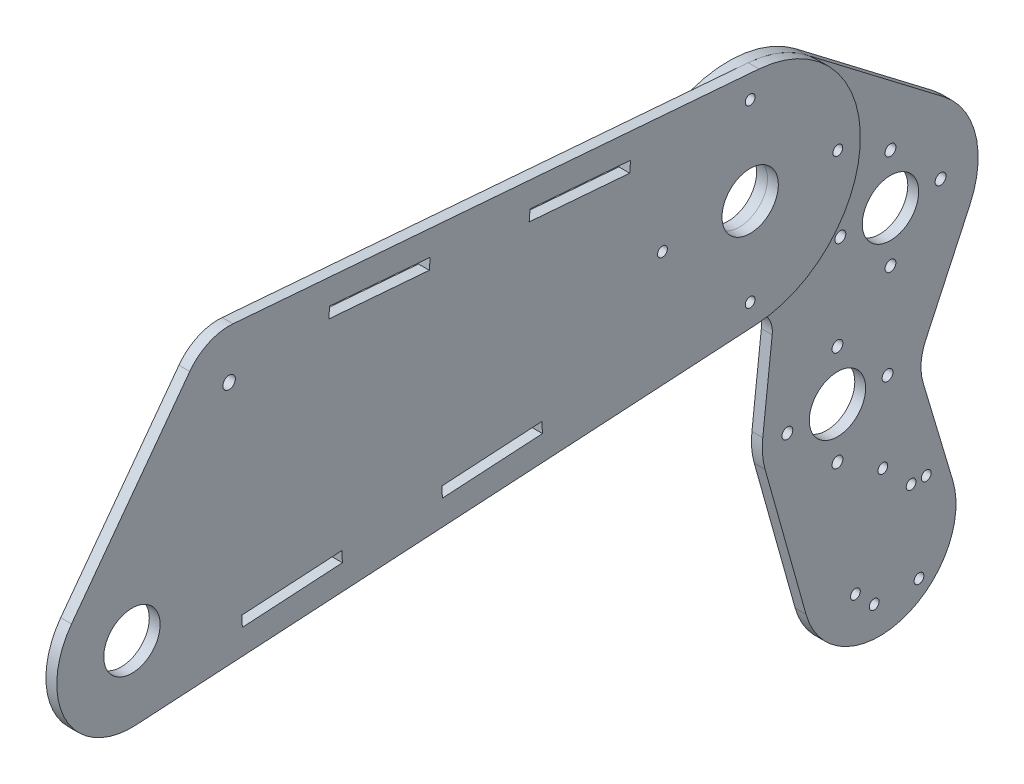
SolidWorks part; units mm, degrees
ref_plane "Alzado" through (0, 0, 0) normal (0, 0, 1) x (1, 0, 0)
ref_plane "Planta" through (0, 0, 0) normal (0, 1, 0) x (1, 0, 0)
ref_plane "Vista lateral" through (0, 0, 0) normal (1, 0, 0) x (0, 0, -1)
sketch "Llantas" plane through (0, 0, 0) normal (1, 0, 0) x (0, 0, -1)
  line L0 (-207.2231, -76.2) -> (-590.1805, -76.2) construction
  line L1 (-359.537, 40.64) -> (359.537, 40.64)
  line L2 (-359.537, 40.64) -> (-359.537, -40.64)
  line L3 (-359.537, -40.64) -> (359.537, -40.64)
  line L4 (359.537, 40.64) -> (359.537, -40.64)
  line L5 (-359.537, 40.64) -> (359.537, -40.64) construction
  line L6 (-359.537, -40.64) -> (359.537, 40.64) construction
  line L7 (-359.537, 101.6) -> (-416.687, 101.6)
  line L8 (-448.437, 69.85) -> (-448.437, 6.35)
  line L9 (-416.687, -25.4) -> (-359.537, -25.4)
  line L10 (-359.537, 101.6) -> (-359.537, -25.4)
  circle A0 centre (-677.037, 152.4) radius 50.8
  circle A2 centre (-207.2231, 0) radius 76.2
  arc A3 (-416.687, 101.6) -> (-448.437, 69.85) centre (-416.687, 69.85) ccw
  arc A4 (-448.437, 6.35) -> (-416.687, -25.4) centre (-416.687, 6.35) ccw
  point P3 (0, 0)
  dimension "D1" = 101.6
  dimension "D5" = 152.4
  dimension "D6" = 177.8
  dimension "D4" = 31.75
  dimension "D11" = 177.8
  dimension "D2" = 81.28
  dimension "D3" = 719.074
  dimension "D7" = 35.56
  dimension "D8" = 88.9
  dimension "D9" = 127
  dimension "D10" = 50.8
sketch "TP" plane through (0, 0, 0) normal (1, 0, 0) x (0, 0, -1)
  line L0 (-365.8418, 207.7402) -> (-679.2386, 171.3713) construction
  line L1 (-361.4386, 169.7977) -> (-674.8354, 133.4287) construction
  line L2 (-289.879, 135.5242) -> (-372.2396, 161.4422) construction
  line L3 (-307.9621, 190.476) -> (-304.3358, 72.1959) construction
  line L4 (-344.3178, 209.9195) -> (-280.5717, 151.6834) construction
  line L5 (-403.4591, 149.8149) -> (-320.7067, 65.2254) construction
  arc A0 (-679.2386, 171.3713) -> (-674.8354, 133.4287) centre (-677.037, 152.4) ccw construction
  arc A2 (-344.3178, 209.9195) -> (-372.2396, 161.4422) centre (-363.6402, 188.7689) ccw construction
  circle A4 centre (-287.0125, 144.6332) radius 30
  arc A5 (-289.879, 135.5242) -> (-280.5717, 151.6834) centre (-287.0125, 144.6332) ccw construction
  arc A7 (-361.4386, 169.7977) -> (-365.8418, 207.7402) centre (-363.6402, 188.7689) ccw construction
  arc A8 (-307.9621, 190.476) -> (-403.4591, 149.8149) centre (-363.6402, 188.7689) ccw construction
  circle A9 centre (-313.8806, 71.9033) radius 30
  arc A10 (-320.7067, 65.2254) -> (-304.3358, 72.1959) centre (-313.8806, 71.9033) ccw construction
  dimension "D1" = 38.1972
  dimension "D2" = 57.2958
  dimension "D3" = 19.0986
  dimension "D4" = 60
  dimension "D5" = 38.1972
  dimension "D8" = 111.4085
  dimension "D9" = 60
  dimension "D10" = 19.0986
sketch "Placa" plane through (0, 0, 0) normal (1, 0, 0) x (0, 0, -1)
  line L0 (-621.0491, 130.2708) -> (-417.8491, 142.3033)
  line L1 (-674.7849, 114.3666) -> (-360.3371, 132.9867)
  line L2 (-329.7252, 233.1801) -> (-260.0347, 179.9602)
  line L3 (-346.965, 118.8981) -> (-351.7448, 76.1356)
  line L4 (-350.566, 61.6178) -> (-329.8243, -12.3619)
  line L5 (-246.7183, 125.8667) -> (-279.3428, 55.8177)
  line L6 (-277.3702, 82.7937) -> (-255.4086, 9.167)
  line L7 (-359.537, 40.64) -> (-359.537, -40.64) construction
  line L8 (-359.537, 40.64) -> (359.537, 40.64) construction
  line L9 (-359.537, -40.64) -> (359.537, -40.64) construction
  line L10 (-647.7191, 255.9522) -> (-707.6477, 175.0847)
  line L11 (-625.7904, 265.9135) -> (-359.1604, 244.4691)
  line L12 (-418.1742, 147.7937) -> (-621.3742, 135.7612)
  line L13 (-621.3742, 135.7612) -> (-621.0491, 130.2708)
  line L14 (-418.1742, 147.7937) -> (-417.8491, 142.3033)
  line L15 (-627.4528, 253.3062) -> (-424.2528, 236.9633)
  line L16 (-424.2528, 236.9633) -> (-424.6937, 231.481)
  line L17 (-424.6937, 231.481) -> (-627.8937, 247.8239)
  line L18 (-627.8937, 247.8239) -> (-627.4528, 253.3062)
  line L19 (-570.663, 138.7641) -> (-570.3379, 133.2737)
  line L20 (-519.9519, 141.7669) -> (-519.6267, 136.2766)
  line L22 (-469.2407, 144.7698) -> (-468.9156, 139.2794)
  line L23 (-576.8163, 249.2336) -> (-577.2572, 243.7513)
  line L24 (-525.8528, 245.1347) -> (-526.2937, 239.6524)
  line L25 (-475.6572, 235.5799) -> (-475.2163, 241.0622)
  circle A0 centre (-677.037, 152.4) radius 14.2875
  circle A1 centre (-363.6402, 188.7689) radius 14.2875
  circle A3 centre (-287.0125, 144.6332) radius 14.2875
  circle A4 centre (-313.8806, 71.9033) radius 14.2875
  circle A5 centre (-677.037, 152.4) radius 38.1
  circle A6 centre (-313.8806, 71.9033) radius 38.1
  circle A7 centre (-287.0125, 144.6332) radius 44.45
  circle A8 centre (-363.6402, 188.7689) radius 55.88
  arc A9 (-346.965, 118.8981) -> (-360.3371, 132.9867) centre (-359.5863, 120.3089) ccw
  circle A15 centre (-313.8806, 71.9033) radius 25.4 construction
  circle A16 centre (-313.8806, 97.3033) radius 2.75
  circle A17 centre (-288.4806, 71.9033) radius 2.75
  circle A18 centre (-313.8806, 46.5033) radius 2.75
  circle A19 centre (-339.2806, 71.9033) radius 2.75
  circle A20 centre (-287.0125, 144.6332) radius 25.4 construction
  circle A21 centre (-287.0125, 170.0332) radius 2.75
  circle A22 centre (-261.6125, 144.6332) radius 2.75
  circle A23 centre (-287.0125, 119.2332) radius 2.75
  circle A24 centre (-312.4125, 144.6332) radius 2.75
  circle A25 centre (-292.5275, -1.905) radius 38.735
  circle A26 centre (-268.859, 18.034) radius 2.4892
  circle A27 centre (-276.5298, 18.034) radius 2.4892
  circle A28 centre (-290.8808, 32.258) radius 2.4892
  circle A29 centre (-272.542, -25.273) radius 2.4892
  circle A30 centre (-295.275, -25.273) radius 2.4892
  circle A31 centre (-304.8, -16.002) radius 2.4892
  circle A32 centre (-363.6402, 188.7689) radius 44.45 construction
  circle A33 centre (-363.6402, 233.2189) radius 2.4892
  circle A34 centre (-319.1902, 188.7689) radius 2.4892
  circle A35 centre (-363.6402, 144.3189) radius 2.4892
  circle A36 centre (-408.0902, 188.7689) radius 2.4892
  arc A37 (-625.7904, 265.9135) -> (-647.7191, 255.9522) centre (-627.78, 241.1759) ccw
  circle A38 centre (-627.78, 241.1759) radius 3.175
  point P39 (-286.3101, 144.2797)
  point P40 (-313.8806, 71.9033)
  point P50 (-287.0125, 144.6332)
  point P84 (-363.6402, 188.7689)
  dimension "D1" = 28.575
  dimension "D2" = 76.2
  dimension "D3" = 111.76
  dimension "D4" = 88.9
  dimension "D5" = 76.2
  dimension "D6" = 12.7
  dimension "D7" = 50.8
  dimension "D8" = 5.5
  dimension "D10" = 50.8
  dimension "D11" = 5.5
  dimension "D13" = 77.47
  dimension "D15" = 90.678
  dimension "D17" = 4.9784
  dimension "D18" = 8.382
  dimension "D19" = 68.6562
  dimension "D20" = 15.367
  dimension "D21" = 24.638
  dimension "D22" = 86.995
  dimension "D23" = 64.262
  dimension "D24" = 54.737
  dimension "D25" = 77.47
  dimension "D26" = 88.9
  dimension "D27" = 4.9784
  dimension "D29" = 49.635
  dimension "D30" = 6.35
  dimension "D14" = 20.1168
  dimension "D16" = 83.0072
  dimension "D31" = 12.7
  dimension "D32" = 5.5
  dimension "D33" = 203.2
  dimension "D34" = 50.07
  dimension "D35" = 266.63
  dimension "D36" = 39.3235
  dimension "D37" = 5.5
  dimension "D38" = 203.2
  dimension "D39" = 201.5376
  dimension "D40" = 12.7
  dimension "D41" = 50.8
  dimension "D42" = 50.8
  dimension "D44" = 50.8
  dimension "D45" = 50.8
  dimension "D46" = 50.8
  dimension "D9" = 4
  dimension "D12" = 4
  dimension "D28" = 4
extrude "Extrución Intake" add sketch "Placa" along normal blind 5.5 contours A5 A0 | A8 A5 L1 | A8 A7 A1 | A7 A8 | L23 L15 L18 L17 | L17 L25 L15 L24 | L12 L22 L0 L14 | L20 L12 L19 L0 region at (0, 137.5203, 545.1449) region at (0, 143.5366, 443.5449) region at (0, 191.5882, 538.6595) region at (0, 134.7777, 709.5963) region at (0, 189.342, 417.9367) region at (0, 163.7789, 320.2531) region at (0, 248.5287, 602.355) region at (0, 240.3573, 500.755)
extrude "Extrución Pibote" add sketch "Placa<6>" against normal blind 5.5 separate body contours A8 A7 A1 | A9 L3 A6 A7 A8 | A7 A6 A4 | A8 A7 A6 A3 | A6 A7 | A8 A7 L2 | A7 A8 | A7 A6 L5 region at (0, 189.342, 417.9367) region at (0, 117.8094, 337.7808) region at (0, 160.2514, 314.1287) region at (0, 163.7789, 320.2531) region at (0, 199.8987, 298.1169) region at (0, 101.9266, 302.7893) region at (0, 105.2532, 301.5604) region at (0, 94.1625, 269.7651)
sketch "Placa<6>" plane through (0, 0, 0) normal (1, 0, 0) x (0, 0, -1) same geometry as "Placa"
extrude "Saliente-Extruir4" add sketch "Placa<8>" against normal blind 5.5 contours A7 A6 A19 A18 A17 A16 A4 | A6 A7 | A25 A6 L4 | A25 L6 L5 A6 | A6 L5 L6 | A25 A31 A30 A29 A28 A27 A26 region at (0, 101.9266, 302.7893) region at (0, 105.2532, 301.5604) region at (0, 27.0452, 331.9613) region at (0, 69.0845, 275.331) region at (0, -1.9609, 292.7234) region at (0, 42.6078, 274.6145)
sketch "Placa<8>" plane through (0, 0, 0) normal (1, 0, 0) x (0, 0, -1) same geometry as "Placa"
fillet "Redondeo1" radius 25.4 1 edges at (-2.75, 68.9312, 273.2353)
sketch "Croquis1" [suppressed] plane through (5.5, 0, 0) normal (1, 0, 0) x (0, 0, -1)
  line L0 (-570.4115, 138.7693) -> (-519.6115, 141.7775)
  line L1 (-519.6115, 141.7775) -> (-519.6115, 136.2775)
  line L2 (-519.6115, 136.2775) -> (-570.4115, 133.2693)
  line L3 (-570.4115, 133.2693) -> (-570.4115, 138.7693)
extrude "Saliente-Extruir5" [suppressed] add sketch "Croquis1" along normal blind 76.2 separate body
sketch "Croquis2" [suppressed] plane through (0, 0, 570.4115) normal (0, 0, 1) x (1, 0, 0)
  line L0 (5.5, 138.7693) -> (5.5, 133.2693)
  line L1 (5.5, 133.2693) -> (73.572, 133.2693)
  line L2 (81.7, 133.2693) -> (5.5, 133.2693) construction
  line L3 (73.572, 133.2693) -> (73.572, 138.7693)
  line L4 (81.7, 138.7693) -> (5.5, 138.7693) construction
  line L5 (73.572, 138.7693) -> (5.5, 138.7693)
  line L6 (81.7, 138.7693) -> (81.7, 133.2693) construction
  dimension "D1" = 8.128
sketch "Croquis3" [suppressed] plane through (0, 166.4626, 9.8571) normal (0, 0.9983, 0.0591) x (1, 0, 0)
  line L0 (-7.2, -561.5363) -> (-7.2, -608.9776)
  line L1 (-7.2, -608.9776) -> (5.5, -608.9776)
  line L2 (5.5, -608.9776) -> (5.5, -634.3776)
  line L3 (5.5, -631.4568) -> (5.5, -608.9776) construction
  line L4 (5.5, -634.3776) -> (96.94, -634.3776)
  line L5 (96.94, -634.3776) -> (96.94, -608.9776)
  line L6 (96.94, -608.9776) -> (109.9452, -608.9776)
  line L7 (109.9452, -608.9776) -> (109.9452, -558.1776)
  line L8 (109.9452, -558.1776) -> (97.2452, -558.1776)
  line L9 (97.2452, -558.1776) -> (97.2452, -507.3776)
  line L10 (97.2452, -507.3776) -> (109.7549, -507.3776)
  line L11 (109.7549, -507.3776) -> (109.7549, -456.5776)
  line L12 (109.7549, -456.5776) -> (96.94, -456.5776)
  line L13 (96.94, -456.5776) -> (96.94, -431.1776)
  line L14 (96.94, -431.1776) -> (5.5, -431.1776)
  line L15 (5.5, -431.1776) -> (5.5, -459.7584)
  line L16 (5.5, -459.7584) -> (-7.2, -459.7584)
  line L17 (-7.2, -459.7584) -> (-7.2, -510.7363)
  line L18 (-7.2, -510.7363) -> (5.5, -510.7363)
  line L19 (5.5, -510.7363) -> (5.5, -561.5363)
  line L20 (5.5, -561.5363) -> (-7.2, -561.5363)
  dimension "D1" = 91.44
  dimension "D2" = 25.4
  dimension "D3" = 25.4
  dimension "D4" = 91.44
  dimension "D5" = 50.8
  dimension "D6" = 25.4
  dimension "D7" = 12.7
  dimension "D8" = 50.8
  dimension "D9" = 50.8
  dimension "D10" = 50.8
  dimension "D11" = 12.7
extrude "Saliente-Extruir7" [suppressed] add sketch "Croquis3" along normal blind 5.588 separate body
delete or keep bodies "Sólido-Eliminar/Conservar 3" [suppressed] type keep bodies bodies 109
equation "\"D1@TP\"=24*5mm/pi"
equation "\"D2@TP\"=36*5mm/pi"
equation "\"D3@TP\"=12*5mm/pi"
equation "\"D5@TP\"=24*5mm/pi"
equation "\"D6@TP\"=(150*5mm)+1mm"
equation "\"D7@TP\"=(60*5mm)+1mm"
equation "\"D8@TP\"=70*5mm/pi"
equation "\"D10@TP\"=12*5mm/pi"
equation "\"D11@TP\"=(95*5mm)+1mm"
